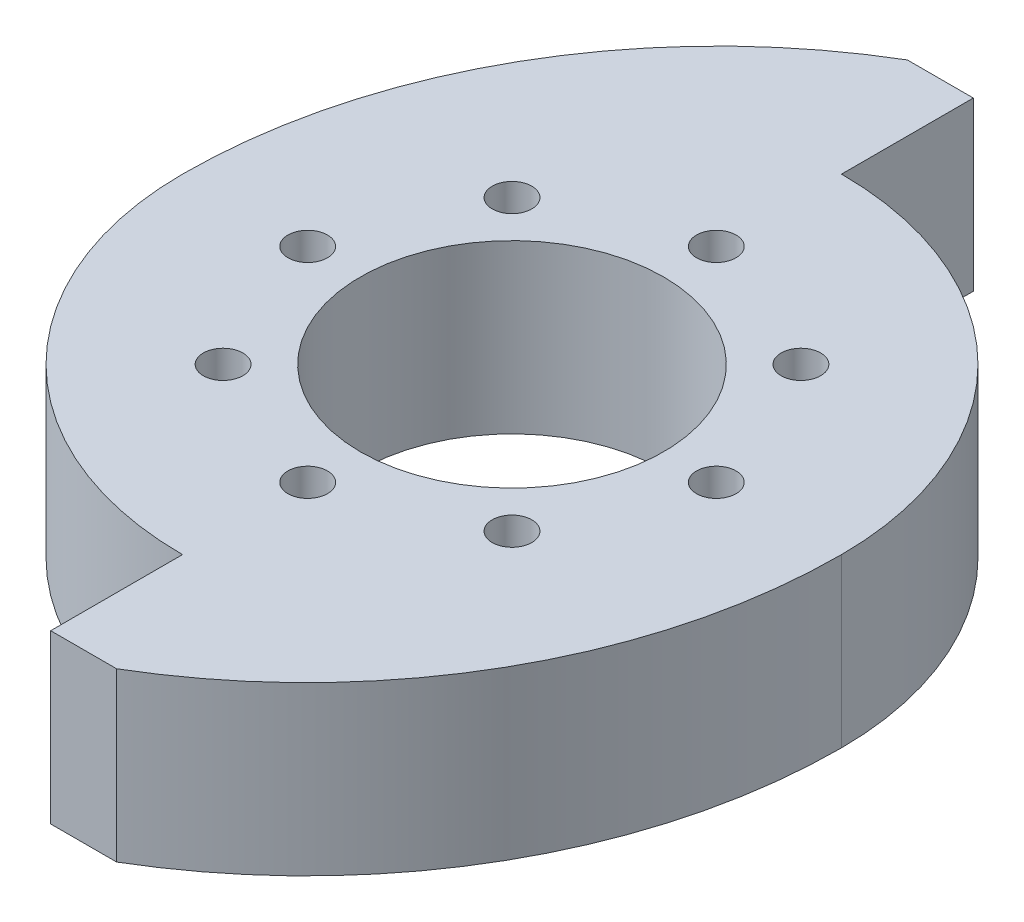
SolidWorks part; units mm, degrees
material "Plain Carbon Steel"
ref_plane "Front Plane" through (0, 0, 0) normal (0, 0, 1) x (1, 0, 0)
ref_plane "Top Plane" through (0, 0, 0) normal (0, 1, 0) x (1, 0, 0)
ref_plane "Right Plane" through (0, 0, 0) normal (1, 0, 0) x (0, 0, -1)
ref_axis "X" through (-88.99, 0, 0) along (1, 0, 0)
ref_axis "Y" through (0, 55, 0) along (0, -1, 0)
ref_axis "Z" through (0, 0, -88.99) along (0, 0, 1)
sketch "Sketch1" plane through (0, 0, 0) normal (0, 1, 0) x (1, 0, 0)
  line L0 (0, 25) -> (0, 35)
  line L1 (0, 35) -> (-5, 35)
  line L2 (0, -25) -> (0, -35)
  line L3 (0, -35) -> (5, -35)
  line L4 (0, 11.5) -> (0, 25) construction
  circle A0 centre (0, 0) radius 25
  arc A1 (-5, 35) -> (-25, 0) centre (15.625, 0) ccw
  arc A2 (5, -35) -> (25, 0) centre (-15.625, 0) ccw
  circle A3 centre (0, 0) radius 11.5
  circle A4 centre (0, 15.5) radius 1.5
  circle A5 centre (10.9602, 10.9602) radius 1.5
  circle A6 centre (15.5, 0) radius 1.5
  circle A7 centre (10.9602, -10.9602) radius 1.5
  circle A8 centre (0, -15.5) radius 1.5
  circle A9 centre (-10.9602, -10.9602) radius 1.5
  circle A10 centre (-15.5, 0) radius 1.5
  circle A11 centre (-10.9602, 10.9602) radius 1.5
  point P16 (0, 0)
  point P35 (0, 0)
  dimension "D1" = 50
  dimension "D4" = 2
  dimension "D5" = 23
  dimension "D6" = 3
  dimension "D2" = 10
  dimension "D3" = 5
  dimension "D8" = 4
  dimension "D7" = 8
extrude "Boss-Extrude1" add sketch "Sketch1" along normal mid plane 12.7 contours A0 A3 | L1 A1 A0 L0 | L3 A2 A0 L2 region at (-9.8514, 0, -25.8127) region at (17.1777, 0, -17.1777) region at (9.8514, 0, 25.8127)
